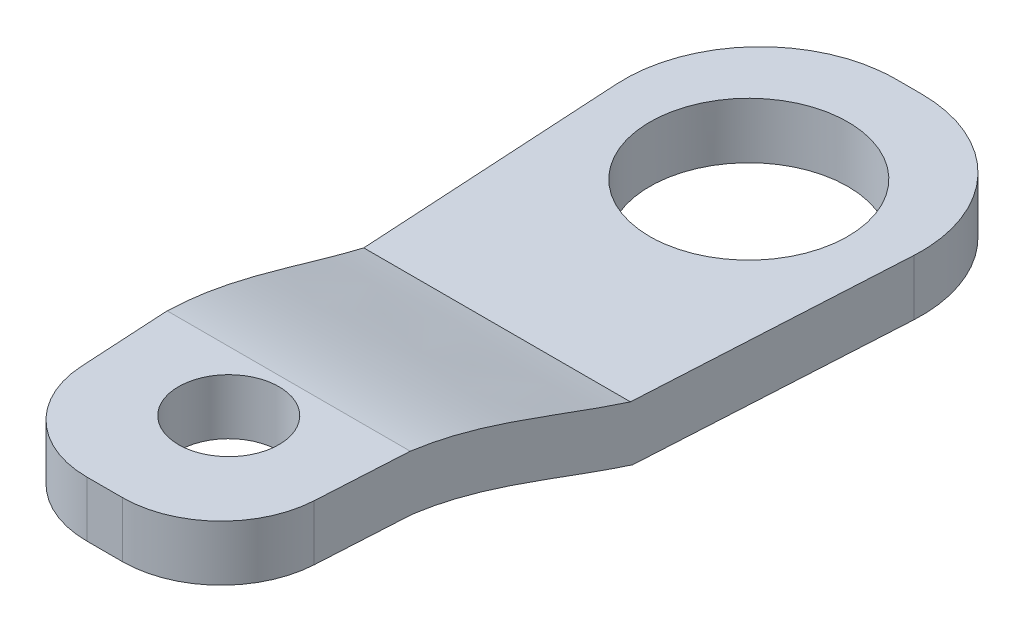
SolidWorks part; units mm, degrees
material "Cast Alloy Steel"
ref_plane "Front Plane" through (0, 0, 0) normal (0, 0, 1) x (1, 0, 0)
ref_plane "Top Plane" through (0, 0, 0) normal (0, 1, 0) x (1, 0, 0)
ref_plane "Right Plane" through (0, 0, 0) normal (1, 0, 0) x (0, 0, -1)
sketch "Sketch1" plane through (0, 0, 0) normal (0, 1, 0) x (1, 0, 0)
  line L1 (-2.2211, 65.2834) -> (-1.1719, 65.2834)
  line L2 (-2.2211, 65.2834) -> (-3.2702, 65.2834)
  line L3 (-2.2211, 0.1517) -> (-3.6615, 0.1517)
  line L4 (-2.2211, 0.1517) -> (-0.7807, 0.1517)
  line L5 (-11.6487, 7.6992) -> (-14.2526, 53.6612)
  line L6 (9.8105, 53.6612) -> (7.2065, 7.6992)
  arc A0 (-1.1719, 65.2834) -> (9.8105, 53.6612) centre (-1.1719, 54.2834) cw
  arc A1 (-3.2702, 65.2834) -> (-14.2526, 53.6612) centre (-3.2702, 54.2834) ccw
  arc A2 (-0.7807, 0.1517) -> (7.2065, 7.6992) centre (-0.7807, 8.1517) ccw
  arc A3 (-3.6615, 0.1517) -> (-11.6487, 7.6992) centre (-3.6615, 8.1517) cw
  circle A4 centre (-2.2211, 52.3234) radius 8.0227
  circle A5 centre (-2.2211, 10.2017) radius 4.0691
  dimension "D1" = 11
  dimension "D2" = 8
extrude "Boss-Extrude1" add sketch "Sketch1" along normal blind 9
sketch "Sketch2" plane through (0, 0, 0) normal (1, 0, 0) x (0, 0, -1)
  line L0 (65.2834, 4.5) -> (65.2834, 9.026)
  line L1 (65.2834, 9.026) -> (15.2337, 8.9611)
  line L2 (32.1225, 4.4757) -> (65.2834, 4.5)
  line L5 (0.1517, 4.5) -> (7.6992, 4.5)
  line L6 (7.6992, 4.5) -> (15.2335, 4.5)
  line L8 (0.1517, 4.5) -> (0.1517, 0)
  line L9 (0.1517, 0) -> (32.1116, 0)
  spline S0 degree 3 poles (15.2337, 8.9611) (20.9978, 8.4646) (26.5354, 6.0289) (32.1118, 4.4611) knots 0.310739 0.310739 0.310739 0.310739 1 1 1 1
  spline S2 degree 3 poles (15.2335, 4.5) (20.9976, 4.0035) (26.5352, 1.5677) (32.1116, 0) knots 0.310739 0.310739 0.310739 0.310739 1 1 1 1
extrude "Cut-Extrude2" cut sketch "Sketch2" against normal blind 80 and the other way blind 80 contours S2 L6 L5 L8 L9 region at (0, 2.0165, -12.8384)
sketch "Sketch3" plane through (0, 0, 0) normal (1, 0, 0) x (0, 0, -1)
  line L0 (65.4412, 9.0597) -> (65.4412, 9.3586)
  line L1 (31.9377, 4.4949) -> (65.4412, 4.5337)
  line L2 (65.4412, 9.3586) -> (15.0596, 9.9858)
  line L3 (65.4412, 9.0597) -> (65.4412, 4.5337)
  line L4 (65.4412, 4.5337) -> (65.1092, 4.5337)
  line L5 (15.0596, 8.9949) -> (0, 8.9949)
  line L6 (0, 8.9949) -> (0, 9.9858)
  line L7 (0, 9.9858) -> (14.7936, 9.9858)
  line L8 (14.7936, 9.9858) -> (15.0596, 9.9858)
  spline S0 degree 3 poles (15.0596, 8.9949) (20.8236, 8.4983) (26.3612, 6.0626) (31.9377, 4.4949) knots 0.310739 0.310739 0.310739 0.310739 1 1 1 1
extrude "Cut-Extrude15" cut sketch "Sketch3" against normal through all and the other way through all contours L3 L0 L2 L8 L7 L6 L5 S0 L1
